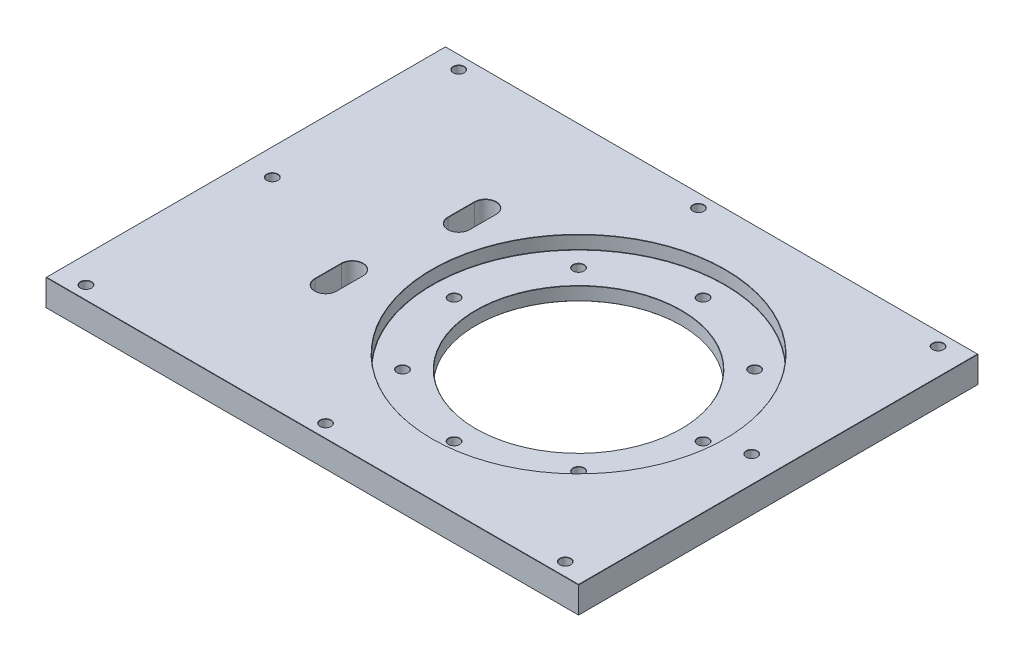
SolidWorks part; units mm, degrees
ref_plane "Front Plane" through (0, 0, 0) normal (0, 0, 1) x (1, 0, 0)
ref_plane "Top Plane" through (0, 0, 0) normal (0, 1, 0) x (1, 0, 0)
ref_plane "Right Plane" through (0, 0, 0) normal (1, 0, 0) x (0, 0, -1)
sketch "Sketch1" plane through (0, 0, 0) normal (0, 1, 0) x (1, 0, 0)
  line L0 (0, 0) -> (-125, 0) construction
  line L1 (65, 70) -> (-115, 70) construction
  line L2 (-125, 75) -> (75, 75)
  line L3 (-125, 75) -> (-125, -75)
  line L4 (-125, -75) -> (75, -75)
  line L5 (75, 75) -> (75, -75)
  line L6 (-125, 75) -> (75, -75) construction
  line L7 (-125, -75) -> (75, 75) construction
  line L9 (65, 70) -> (65, 75) construction
  line L11 (65, 70) -> (75, 70) construction
  line L12 (65, 70) -> (65, -70) construction
  circle A0 centre (0, 0) radius 38.5
  circle A1 centre (0, 0) radius 55
  circle A2 centre (65, 70) radius 2
  circle A3 centre (-115, 70) radius 2
  circle A4 centre (65, -70) radius 2
  circle A5 centre (-115, -70) radius 2
  circle A6 centre (-25, 70) radius 2
  circle A7 centre (-25, -70) radius 2
  circle A8 centre (65, 0) radius 2
  circle A9 centre (-115, 0) radius 2
  point P4 (-25, 0)
  dimension "D1" = 200
  dimension "D3" = 110
  dimension "D4" = 77
  dimension "D8" = 4
  dimension "D6" = 77
  dimension "D7" = 5
  dimension "D2" = 75
  dimension "D5" = 150
  dimension "D9" = 10
  dimension "D10" = 5
extrude "Boss-Extrude1" add sketch "Sketch1" along normal blind 10 contours L5 L2 L3 L4 A4 A3 A2 A1 A5 region at (-25, 0, -72.5)
extrude "Boss-Extrude2" add sketch "Sketch1<3>" along normal blind 5 contours A1 A0 region at (-53.4444, 0, 0)
sketch "Sketch1<3>" plane through (0, 0, 0) normal (0, 1, 0) x (1, 0, 0) same geometry as "Sketch1"
extrude "Boss-Extrude3" add sketch "Sketch1<4>" along normal blind 9 contours A0 region at (0, 0, 0)
sketch "Sketch1<4>" plane through (0, 0, 0) normal (0, 1, 0) x (1, 0, 0) same geometry as "Sketch1"
sketch "Sketch2" plane through (0, 5, 0) normal (0, 1, 0) x (1, 0, 0)
  line L0 (0, 38.5) -> (0, 55) construction
  circle A0 centre (0, 0) radius 38.5 construction
  circle A1 centre (0, 0) radius 38.5 construction
  circle A2 centre (0, 0) radius 55 construction
  circle A11 centre (0, 46.75) radius 2
  circle A12 centre (33.0572, 33.0572) radius 2
  circle A13 centre (46.75, 0) radius 2
  circle A14 centre (33.0572, -33.0572) radius 2
  circle A15 centre (0, -46.75) radius 2
  circle A16 centre (-33.0572, -33.0572) radius 2
  circle A17 centre (-46.75, 0) radius 2
  circle A18 centre (-33.0572, 33.0572) radius 2
  point P27 (8.4497, -3.5)
  point P29 (0, 0)
  dimension "D1" = 8
extrude "Cut-Extrude1" cut sketch "Sketch2" against normal through all
extrude "Cut-Extrude2" cut sketch "Sketch1<5>" along normal through all contours A0 region at (0, 0, 0)
sketch "Sketch1<5>" plane through (0, 0, 0) normal (0, 1, 0) x (1, 0, 0) same geometry as "Sketch1"
sketch "Sketch4" plane through (0, 10, 0) normal (0, 1, 0) x (1, 0, 0)
  line L0 (75, 0) -> (-125, 0) construction
  line L1 (75, 75) -> (75, -75) construction
  line L2 (-125, 75) -> (-125, -75) construction
  line L3 (-65, 30) -> (-65, 20) construction
  line L4 (-61, 30) -> (-61, 20)
  line L5 (-69, 30) -> (-69, 20)
  line L6 (-70, -25) -> (-70, -15) construction
  line L7 (-74, -25) -> (-74, -15)
  line L8 (-66, -25) -> (-66, -15)
  arc A2 (-61, 30) -> (-69, 30) centre (-65, 30) ccw
  arc A7 (-69, 20) -> (-61, 20) centre (-65, 20) ccw
  arc A8 (-74, -25) -> (-66, -25) centre (-70, -25) ccw
  arc A9 (-66, -15) -> (-74, -15) centre (-70, -15) ccw
  point P6 (-65, 30)
  point P9 (-65, 25)
  point P14 (-70, 25)
  point P15 (-70, -20)
  point P16 (-70, -25)
  dimension "D3" = 10
  dimension "D5" = 4
  dimension "D6" = 4
  dimension "D1" = 30
  dimension "D2" = 60
  dimension "D4" = 5
  dimension "D7" = 10
extrude "Cut-Extrude3" cut sketch "Sketch4" against normal through all
chamfer "Chamfer1" distance 0.1 angle 45 60 edges at (-115, 0, 72) (-25, 0, -75) (-125, 0, 0) (-25, 0, 75) (75, 0, 0) (65, 0, -68) (-115, 0, -68) (65, 0, 72) (-33.0572, 0, -31.0572) (-46.75, 0, 2) (-33.0572, 0, 35.0572) (0, 0, 48.75) (33.0572, 0, 35.0572) (46.75, 0, 2) (33.0572, 0, -31.0572) (0, 0, -44.75) (0, 0, 38.5) (-115, 10, 72) (-25, 10, 75) (-125, 10, 0) (-25, 10, -75) (75, 10, 0) (0, 10, 55) (65, 10, -68) (-115, 10, -68) (65, 10, 72) (0, 5, 55) (0, 5, 38.5) (-33.0572, 5, -31.0572) (-46.75, 5, 2) (-33.0572, 5, 35.0572) (0, 5, 48.75) (33.0572, 5, 35.0572) (46.75, 5, 2) (33.0572, 5, -31.0572) (0, 5, -44.75) (-70, 0, 11) (-66, 0, 20) (-70, 0, 29) (-74, 0, 20) (-65, 0, -16) (-69, 0, -25) (-65, 0, -34) (-61, 0, -25) (-66, 10, 20) (-70, 10, 11) (-74, 10, 20) (-70, 10, 29) (-69, 10, -25) (-65, 10, -16) (-61, 10, -25) (-65, 10, -34) (-25, 0, 72) (-25, 0, -68) (-25, 10, 72) (-25, 10, -68) (65, 0, 2) (-115, 0, 2) (65, 10, 2) (-115, 10, 2)
